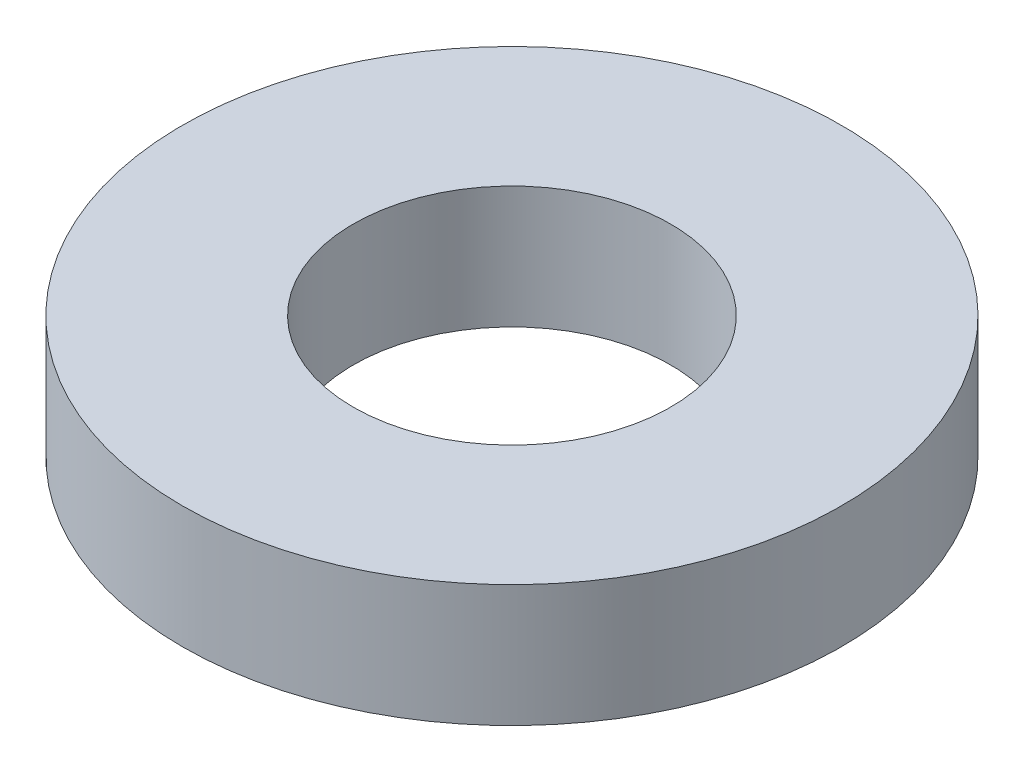
SolidWorks part; units mm, degrees
ref_plane "Front Plane" through (0, 0, 0) normal (0, 0, 1) x (1, 0, 0)
ref_plane "Top Plane" through (0, 0, 0) normal (0, 1, 0) x (1, 0, 0)
ref_plane "Right Plane" through (0, 0, 0) normal (1, 0, 0) x (0, 0, -1)
sketch "Sketch1" plane through (0, 0, 0) normal (0, 1, 0) x (1, 0, 0)
  circle A0 centre (0, 0) radius 67.5
  dimension "FLANGE_OD" = 135
extrude "Boss-Extrude1" add sketch "Sketch1" along normal blind 25
sketch "Sketch2" plane through (0, 0, 0) normal (0, 1, 0) x (1, 0, 0)
  circle A0 centre (0, 0) radius 32.5
  dimension "BORE_D" = 65
extrude "Cut-Extrude1" cut sketch "Sketch2" along normal through all
sketch "Sketch3" plane through (0, 25, 0) normal (0, 1, 0) x (1, 0, 0)
  circle A0 centre (0, 0) radius 20.8328 construction
  circle A1 centre (-20.8328, 0) radius 4.4667
  dimension "BOLT_D" = 8.9334
  dimension "BOLT_PCD" = 41.6656
extrude "Cut-Extrude2" cut sketch "Sketch3" against normal blind 23.7644 rebuild error yes
pattern_circular "CirPattern1" count 6 over 360 rebuild error yes
